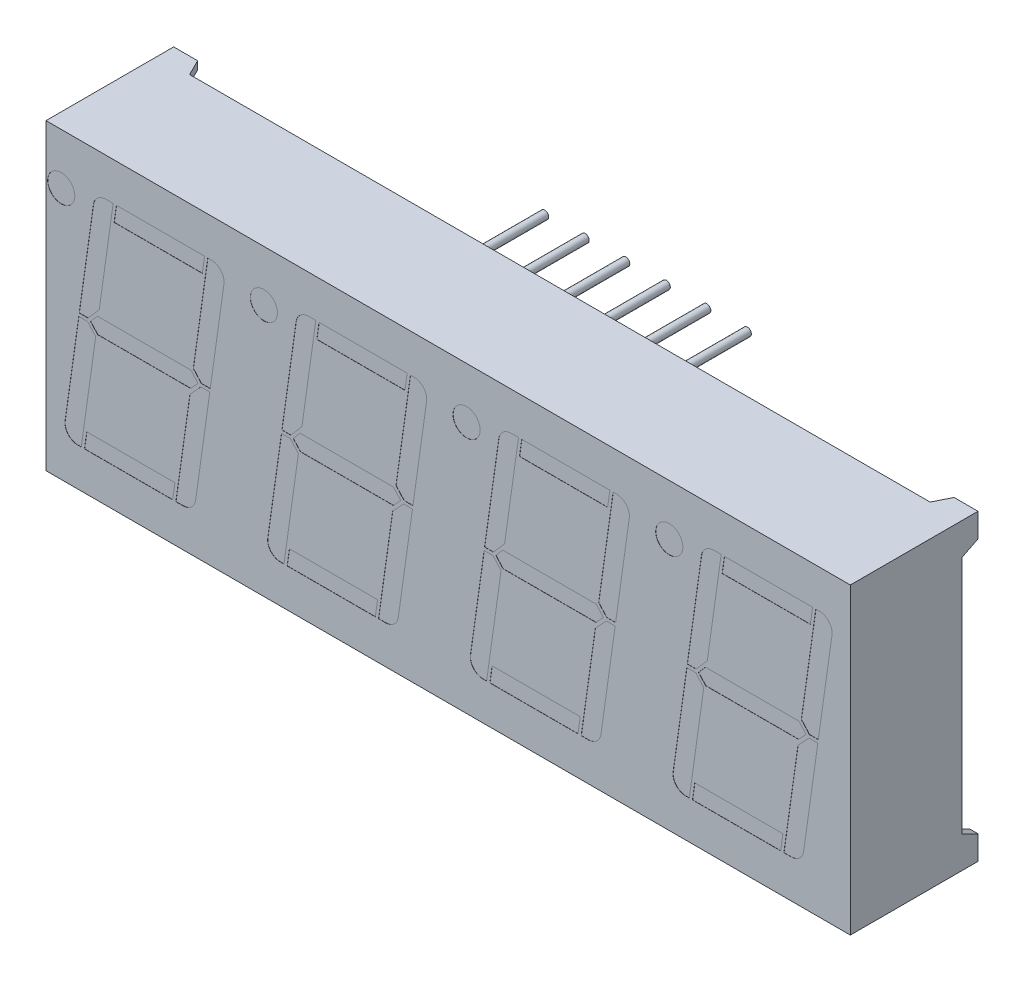
SolidWorks part; units mm, degrees
ref_plane "Front Plane" through (0, 0, 0) normal (0, 0, 1) x (1, 0, 0)
ref_plane "Top Plane" through (0, 0, 0) normal (0, 1, 0) x (1, 0, 0)
ref_plane "Right Plane" through (0, 0, 0) normal (1, 0, 0) x (0, 0, -1)
sketch "Sketch1" plane through (0, 0, 0) normal (0, 1, 0) x (1, 0, 0)
  line L1 (0, 0) -> (50.4, 0)
  line L2 (0, 0) -> (0, 8)
  line L3 (0, 8) -> (50.4, 8)
  line L4 (50.4, 0) -> (50.4, 8)
  dimension "D1" = 8
  dimension "D2" = 50.4
extrude "Boss-Extrude1" add sketch "Sketch1" along normal blind 19
sketch "Sketch2" plane through (0, 0, -8) normal (0, 0, -1) x (-1, 0, 0)
  line L0 (-50.4, 17) -> (-49.9, 17)
  line L1 (-50.4, 19) -> (-50.4, 0) construction
  line L2 (-49.9, 17) -> (-49.9, 18.5)
  line L3 (-49.9, 18.5) -> (-48.4, 18.5)
  line L4 (-48.4, 18.5) -> (-48.4, 19)
  line L5 (-50.4, 19) -> (0, 19) construction
  line L6 (-48.4, 19) -> (-2, 19)
  line L7 (-2, 19) -> (-2, 18.5)
  line L8 (-2, 18.5) -> (-0.5, 18.5)
  line L9 (-0.5, 18.5) -> (-0.5, 17)
  line L10 (-0.5, 17) -> (0, 17)
  line L11 (0, 19) -> (0, 0) construction
  line L12 (0, 17) -> (0, 2)
  line L13 (0, 2) -> (-0.5, 2)
  line L14 (-0.5, 2) -> (-0.5, 0.5)
  line L15 (-0.5, 0.5) -> (-2, 0.5)
  line L16 (-2, 0.5) -> (-2, 0)
  line L17 (-50.4, 0) -> (0, 0) construction
  line L18 (-2, 0) -> (-48.4, 0)
  line L19 (-48.4, 0) -> (-48.4, 0.5)
  line L20 (-48.4, 0.5) -> (-49.9, 0.5)
  line L21 (-49.9, 0.5) -> (-49.9, 2)
  line L22 (-49.9, 2) -> (-50.4, 2)
  line L23 (-50.4, 2) -> (-50.4, 17)
  line L24 (-49.9, 17) -> (-49.9, 2) construction
  line L25 (-48.4, 0.5) -> (-2, 0.5) construction
  line L26 (-0.5, 2) -> (-0.5, 17) construction
  line L27 (-2, 18.5) -> (-48.4, 18.5) construction
  line L28 (-2, 0.5) -> (-2, 18.5) construction
  line L29 (-0.5, 17) -> (-49.9, 17) construction
  line L30 (-48.4, 0.5) -> (-48.4, 18.5) construction
  line L31 (-49.9, 2) -> (-0.5, 2) construction
  dimension "D1" = 0.5
  dimension "D2" = 2
  dimension "D3" = 2
  dimension "D4" = 2
  dimension "D5" = 2
extrude "Cut-Extrude1" cut sketch "Sketch2" against normal blind 1
chamfer "Chamfer1" distance 0.5 distance2 1 8 edges at (50.15, 2, -8) (48.4, 0.25, -8) (2, 0.25, -8) (0.25, 2, -8) (2, 18.75, -8) (0.25, 17, -8) (48.4, 18.75, -8) (50.15, 17, -8) first distance on face at (49.5667, 0.8333, -8) first distance on face at (0.8333, 0.8333, -8) first distance on face at (0.8333, 18.1667, -8) first distance on face at (49.5667, 18.1667, -8)
sketch "Sketch3" plane through (0, 0, -7) normal (0, 0, -1) x (-1, 0, 0)
  line L21 (-49.9, 0.5) -> (-0.5, 0.5)
  line L22 (-49.9, 0.5) -> (-49.9, 18.5)
  line L23 (-49.9, 18.5) -> (-0.5, 18.5)
  line L24 (-0.5, 0.5) -> (-0.5, 18.5)
extrude "Cut-Extrude2" cut sketch "Sketch3" against normal blind 0.1
sketch "Sketch4" plane through (0, 0, -6.9) normal (0, 0, -1) x (-1, 0, 0)
  line L0 (-49.9, 9.5) -> (-0.5, 9.5) construction
  line L1 (-49.9, 2) -> (-49.9, 17) construction
  line L2 (-0.5, 0.5) -> (-0.5, 18.5) construction
  line L3 (-49.9, 17.12) -> (-0.5, 17.12) construction
  line L4 (-49.9, 18.5) -> (-49.9, 0.5) construction
  line L5 (-0.5, 1.88) -> (-49.9, 1.88) construction
  line L6 (-25.2, 1.88) -> (-25.2, 17.12) construction
  line L7 (-26.47, 17.12) -> (-25.2, 15.85) construction
  line L8 (-25.2, 15.85) -> (-23.93, 17.12) construction
  line L9 (-31.55, 17.12) -> (-31.55, 1.88) construction
  line L10 (-29.01, 17.12) -> (-29.01, 1.88) construction
  line L11 (-26.47, 17.12) -> (-26.47, 1.88) construction
  line L12 (-23.93, 17.12) -> (-23.93, 1.88) construction
  line L13 (-21.39, 17.12) -> (-21.39, 1.88) construction
  line L14 (-18.85, 17.12) -> (-18.85, 1.88) construction
  circle A0 centre (-31.55, 17.12) radius 0.25
  circle A1 centre (-29.01, 17.12) radius 0.25
  circle A2 centre (-26.47, 17.12) radius 0.25
  circle A3 centre (-23.93, 17.12) radius 0.25
  circle A4 centre (-21.39, 17.12) radius 0.25
  circle A5 centre (-18.85, 17.12) radius 0.25
  circle A6 centre (-31.55, 1.88) radius 0.25
  circle A7 centre (-29.01, 1.88) radius 0.25
  circle A8 centre (-26.47, 1.88) radius 0.25
  circle A10 centre (-23.93, 1.88) radius 0.25
  circle A11 centre (-21.39, 1.88) radius 0.25
  circle A12 centre (-18.85, 1.88) radius 0.25
  point P30 (-25.2, 9.5)
  dimension "D6" = 0.5
  dimension "D1" = 15.24
  dimension "D2" = 2.54
  dimension "D3" = 2.54
  dimension "D4" = 2.54
  dimension "D5" = 2.54
  dimension "D7" = 2.54
  dimension "D8" = 45
  dimension "D9" = 45
extrude "Boss-Extrude2" add sketch "Sketch4" along normal blind 5.5
sketch "Sketch5" plane through (0, 0, 0) normal (0, 0, 1) x (1, 0, 0)
  line L0 (0, 9.5) -> (50.4, 9.5) construction
  line L1 (0, 19) -> (0, 0) construction
  line L2 (50.4, 19) -> (50.4, 0) construction
  line L3 (49.2488, 15.6987) -> (48.3916, 9.6)
  line L4 (0, 19) -> (50.4, 19) construction
  line L5 (0, 0) -> (50.4, 0) construction
  line L6 (6.15, 19) -> (6.15, 0) construction
  line L7 (18.85, 0) -> (18.85, 19) construction
  line L8 (31.55, 0) -> (31.55, 19) construction
  line L9 (44.25, 0) -> (44.25, 19) construction
  line L10 (25.2, 9.5) -> (25.2, 19) construction
  line L11 (25.2, 14.25) -> (18.85, 14.25) construction
  line L12 (25.2, 14.25) -> (31.55, 14.25) construction
  line L13 (50.4, 16.61) -> (0, 16.61) construction
  line L14 (50.4, 2.39) -> (0, 2.39) construction
  line L15 (49.4, 16.61) -> (49.4, 9.5) construction
  line L16 (49.4, 9.5) -> (49.4, 2.39) construction
  line L17 (48.3916, 9.6) -> (47.8362, 9.6)
  line L18 (47.8362, 9.6) -> (47.3296, 10.1627)
  line L19 (47.3296, 10.1627) -> (48.2357, 16.61)
  line L20 (48.3916, 9.6) -> (48.3635, 9.4) construction
  line L21 (48.3635, 9.4) -> (47.4751, 3.0787)
  line L22 (48.3635, 9.4) -> (47.8081, 9.4)
  line L23 (47.8081, 9.4) -> (47.1185, 8.6605)
  line L24 (47.1185, 8.6605) -> (46.2372, 2.39)
  line L25 (47.6279, 9.5) -> (47.1617, 9)
  line L26 (47.1617, 9) -> (41.3383, 9)
  line L27 (41.3383, 9) -> (40.8881, 9.5)
  line L28 (40.8881, 9.5) -> (41.3223, 10)
  line L29 (41.3223, 10) -> (47.1777, 10)
  line L30 (47.1777, 10) -> (47.6279, 9.5)
  line L31 (44.25, 9) -> (44.25, 10) construction
  line L32 (47.8081, 9.4) -> (47.8362, 9.6) construction
  line L33 (40.709, 9.4) -> (40.7372, 9.6) construction
  line L34 (46.2372, 2.39) -> (46.6829, 2.39)
  line L35 (46.0353, 2.39) -> (46.1758, 3.39)
  line L36 (46.1758, 3.39) -> (40.6521, 3.39)
  line L37 (40.6521, 3.39) -> (40.5115, 2.39)
  line L38 (40.5115, 2.39) -> (46.0353, 2.39)
  line L39 (43.4139, 3.39) -> (43.4139, 2.39) construction
  line L43 (40.1536, 9.4) -> (39.2965, 3.3013)
  line L44 (40.1536, 9.4) -> (40.1818, 9.6) construction
  line L45 (47.3296, 10.1627) -> (47.1185, 8.6605) construction
  line L46 (40.3096, 2.39) -> (41.2157, 8.8373)
  line L47 (40.1818, 9.6) -> (41.0702, 15.9213)
  line L48 (41.436, 10.4048) -> (42.308, 16.61)
  line L49 (41.2157, 8.8373) -> (41.436, 10.4048) construction
  line L50 (41.436, 10.4048) -> (40.7372, 9.6)
  line L51 (40.7372, 9.6) -> (40.1818, 9.6)
  line L52 (44.25, 9.5) -> (44.2005, 9.4505) construction
  line L53 (36.5488, 15.6987) -> (35.6916, 9.6)
  line L54 (41.2157, 8.8373) -> (40.709, 9.4)
  line L55 (40.709, 9.4) -> (40.1536, 9.4)
  line L56 (40.3096, 2.39) -> (40.0887, 2.39)
  line L57 (42.308, 16.61) -> (41.8624, 16.61)
  line L58 (48.2357, 16.61) -> (48.4565, 16.61)
  line L59 (46.1758, 3.39) -> (47.8932, 15.61) construction
  line L60 (40.6521, 3.39) -> (42.3695, 15.61) construction
  line L61 (47.8932, 15.61) -> (42.3695, 15.61)
  line L62 (42.3695, 15.61) -> (42.51, 16.61)
  line L63 (47.8932, 15.61) -> (48.0338, 16.61)
  line L64 (48.0338, 16.61) -> (42.51, 16.61)
  line L65 (35.6916, 9.6) -> (35.1362, 9.6)
  line L66 (35.1362, 9.6) -> (34.6296, 10.1627)
  line L67 (34.6296, 10.1627) -> (35.5357, 16.61)
  line L68 (35.6635, 9.4) -> (34.7751, 3.0787)
  line L69 (35.6635, 9.4) -> (35.1081, 9.4)
  line L70 (35.1081, 9.4) -> (34.4185, 8.6605)
  line L71 (34.4185, 8.6605) -> (33.5372, 2.39)
  line L72 (34.9279, 9.5) -> (34.4617, 9)
  line L73 (34.4617, 9) -> (28.6383, 9)
  line L74 (28.6383, 9) -> (28.1881, 9.5)
  line L75 (28.1881, 9.5) -> (28.6223, 10)
  line L76 (28.6223, 10) -> (34.4777, 10)
  line L77 (34.4777, 10) -> (34.9279, 9.5)
  line L78 (33.5372, 2.39) -> (33.9829, 2.39)
  line L79 (33.3353, 2.39) -> (33.4758, 3.39)
  line L80 (33.4758, 3.39) -> (27.9521, 3.39)
  line L81 (27.9521, 3.39) -> (27.8115, 2.39)
  line L82 (27.8115, 2.39) -> (33.3353, 2.39)
  line L83 (27.4536, 9.4) -> (26.5965, 3.3013)
  line L84 (27.6096, 2.39) -> (28.5157, 8.8373)
  line L85 (27.4818, 9.6) -> (28.3702, 15.9213)
  line L86 (28.736, 10.4048) -> (29.608, 16.61)
  line L87 (28.736, 10.4048) -> (28.0372, 9.6)
  line L88 (28.0372, 9.6) -> (27.4818, 9.6)
  line L89 (28.5157, 8.8373) -> (28.009, 9.4)
  line L90 (28.009, 9.4) -> (27.4536, 9.4)
  line L91 (27.6096, 2.39) -> (27.3887, 2.39)
  line L92 (29.608, 16.61) -> (29.1624, 16.61)
  line L93 (35.5357, 16.61) -> (35.7565, 16.61)
  line L94 (35.1932, 15.61) -> (29.6695, 15.61)
  line L95 (29.6695, 15.61) -> (29.81, 16.61)
  line L96 (35.1932, 15.61) -> (35.3338, 16.61)
  line L97 (35.3338, 16.61) -> (29.81, 16.61)
  line L98 (35.6916, 9.6) -> (35.6635, 9.4) construction
  line L99 (31.55, 9) -> (31.55, 10) construction
  line L100 (35.1081, 9.4) -> (35.1362, 9.6) construction
  line L101 (28.009, 9.4) -> (28.0372, 9.6) construction
  line L102 (30.7139, 3.39) -> (30.7139, 2.39) construction
  line L103 (27.4536, 9.4) -> (27.4818, 9.6) construction
  line L104 (34.6296, 10.1627) -> (34.4185, 8.6605) construction
  line L105 (28.5157, 8.8373) -> (28.736, 10.4048) construction
  line L106 (31.55, 9.5) -> (31.5005, 9.4505) construction
  line L107 (33.4758, 3.39) -> (35.1932, 15.61) construction
  line L108 (27.9521, 3.39) -> (29.6695, 15.61) construction
  line L109 (23.8488, 15.6987) -> (22.9916, 9.6)
  line L110 (22.9916, 9.6) -> (22.4362, 9.6)
  line L111 (22.4362, 9.6) -> (21.9296, 10.1627)
  line L112 (21.9296, 10.1627) -> (22.8357, 16.61)
  line L113 (22.9635, 9.4) -> (22.0751, 3.0787)
  line L114 (22.9635, 9.4) -> (22.4081, 9.4)
  line L115 (22.4081, 9.4) -> (21.7185, 8.6605)
  line L116 (21.7185, 8.6605) -> (20.8372, 2.39)
  line L117 (22.2279, 9.5) -> (21.7617, 9)
  line L118 (21.7617, 9) -> (15.9383, 9)
  line L119 (15.9383, 9) -> (15.4881, 9.5)
  line L120 (15.4881, 9.5) -> (15.9223, 10)
  line L121 (15.9223, 10) -> (21.7777, 10)
  line L122 (21.7777, 10) -> (22.2279, 9.5)
  line L123 (20.8372, 2.39) -> (21.2829, 2.39)
  line L124 (20.6353, 2.39) -> (20.7758, 3.39)
  line L125 (20.7758, 3.39) -> (15.2521, 3.39)
  line L126 (15.2521, 3.39) -> (15.1115, 2.39)
  line L127 (15.1115, 2.39) -> (20.6353, 2.39)
  line L128 (14.7536, 9.4) -> (13.8965, 3.3013)
  line L129 (14.9096, 2.39) -> (15.8157, 8.8373)
  line L130 (14.7818, 9.6) -> (15.6702, 15.9213)
  line L131 (16.036, 10.4048) -> (16.908, 16.61)
  line L132 (16.036, 10.4048) -> (15.3372, 9.6)
  line L133 (15.3372, 9.6) -> (14.7818, 9.6)
  line L134 (15.8157, 8.8373) -> (15.309, 9.4)
  line L135 (15.309, 9.4) -> (14.7536, 9.4)
  line L136 (14.9096, 2.39) -> (14.6887, 2.39)
  line L137 (16.908, 16.61) -> (16.4624, 16.61)
  line L138 (22.8357, 16.61) -> (23.0565, 16.61)
  line L139 (22.4932, 15.61) -> (16.9695, 15.61)
  line L140 (16.9695, 15.61) -> (17.11, 16.61)
  line L141 (22.4932, 15.61) -> (22.6338, 16.61)
  line L142 (22.6338, 16.61) -> (17.11, 16.61)
  line L143 (22.9916, 9.6) -> (22.9635, 9.4) construction
  line L144 (18.85, 9) -> (18.85, 10) construction
  line L145 (22.4081, 9.4) -> (22.4362, 9.6) construction
  line L146 (15.309, 9.4) -> (15.3372, 9.6) construction
  line L147 (18.0139, 3.39) -> (18.0139, 2.39) construction
  line L148 (14.7536, 9.4) -> (14.7818, 9.6) construction
  line L149 (21.9296, 10.1627) -> (21.7185, 8.6605) construction
  line L150 (15.8157, 8.8373) -> (16.036, 10.4048) construction
  line L151 (18.85, 9.5) -> (18.8005, 9.4505) construction
  line L152 (20.7758, 3.39) -> (22.4932, 15.61) construction
  line L153 (15.2521, 3.39) -> (16.9695, 15.61) construction
  line L154 (11.1488, 15.6987) -> (10.2916, 9.6)
  line L155 (10.2916, 9.6) -> (9.7362, 9.6)
  line L156 (9.7362, 9.6) -> (9.2296, 10.1627)
  line L157 (9.2296, 10.1627) -> (10.1357, 16.61)
  line L158 (10.2635, 9.4) -> (9.3751, 3.0787)
  line L159 (10.2635, 9.4) -> (9.7081, 9.4)
  line L160 (9.7081, 9.4) -> (9.0185, 8.6605)
  line L161 (9.0185, 8.6605) -> (8.1372, 2.39)
  line L162 (9.5279, 9.5) -> (9.0617, 9)
  line L163 (9.0617, 9) -> (3.2383, 9)
  line L164 (3.2383, 9) -> (2.7881, 9.5)
  line L165 (2.7881, 9.5) -> (3.2223, 10)
  line L166 (3.2223, 10) -> (9.0777, 10)
  line L167 (9.0777, 10) -> (9.5279, 9.5)
  line L168 (8.1372, 2.39) -> (8.5829, 2.39)
  line L169 (7.9353, 2.39) -> (8.0758, 3.39)
  line L170 (8.0758, 3.39) -> (2.5521, 3.39)
  line L171 (2.5521, 3.39) -> (2.4115, 2.39)
  line L172 (2.4115, 2.39) -> (7.9353, 2.39)
  line L173 (2.0536, 9.4) -> (1.1965, 3.3013)
  line L174 (2.2096, 2.39) -> (3.1157, 8.8373)
  line L175 (2.0818, 9.6) -> (2.9702, 15.9213)
  line L176 (3.336, 10.4048) -> (4.208, 16.61)
  line L177 (3.336, 10.4048) -> (2.6372, 9.6)
  line L178 (2.6372, 9.6) -> (2.0818, 9.6)
  line L179 (3.1157, 8.8373) -> (2.609, 9.4)
  line L180 (2.609, 9.4) -> (2.0536, 9.4)
  line L181 (2.2096, 2.39) -> (1.9887, 2.39)
  line L182 (4.208, 16.61) -> (3.7624, 16.61)
  line L183 (10.1357, 16.61) -> (10.3565, 16.61)
  line L184 (9.7932, 15.61) -> (4.2695, 15.61)
  line L185 (4.2695, 15.61) -> (4.41, 16.61)
  line L186 (9.7932, 15.61) -> (9.9338, 16.61)
  line L187 (9.9338, 16.61) -> (4.41, 16.61)
  line L188 (10.2916, 9.6) -> (10.2635, 9.4) construction
  line L189 (6.15, 9) -> (6.15, 10) construction
  line L190 (9.7081, 9.4) -> (9.7362, 9.6) construction
  line L191 (2.609, 9.4) -> (2.6372, 9.6) construction
  line L192 (5.3139, 3.39) -> (5.3139, 2.39) construction
  line L193 (2.0536, 9.4) -> (2.0818, 9.6) construction
  line L194 (9.2296, 10.1627) -> (9.0185, 8.6605) construction
  line L195 (3.1157, 8.8373) -> (3.336, 10.4048) construction
  line L196 (6.15, 9.5) -> (6.1005, 9.4505) construction
  line L197 (8.0758, 3.39) -> (9.7932, 15.61) construction
  line L198 (2.5521, 3.39) -> (4.2695, 15.61) construction
  line L199 (39.0545, 16.61) -> (39.0545, 15.81) construction
  line L200 (39.0545, 15.81) -> (41.0545, 15.81) construction
  line L201 (26.3545, 15.81) -> (28.3545, 15.81) construction
  line L202 (26.3545, 15.81) -> (26.3545, 16.61) construction
  arc A0 (48.4565, 16.61) -> (49.2488, 15.6987) centre (48.4565, 15.81) cw
  arc A2 (47.4751, 3.0787) -> (46.6829, 2.39) centre (46.6829, 3.19) cw
  arc A3 (39.2965, 3.3013) -> (40.0887, 2.39) centre (40.0887, 3.19) ccw
  arc A4 (41.8624, 16.61) -> (41.0702, 15.9213) centre (41.8624, 15.81) ccw
  arc A5 (35.7565, 16.61) -> (36.5488, 15.6987) centre (35.7565, 15.81) cw
  arc A6 (34.7751, 3.0787) -> (33.9829, 2.39) centre (33.9829, 3.19) cw
  arc A7 (26.5965, 3.3013) -> (27.3887, 2.39) centre (27.3887, 3.19) ccw
  arc A8 (29.1624, 16.61) -> (28.3702, 15.9213) centre (29.1624, 15.81) ccw
  arc A9 (23.0565, 16.61) -> (23.8488, 15.6987) centre (23.0565, 15.81) cw
  arc A10 (22.0751, 3.0787) -> (21.2829, 2.39) centre (21.2829, 3.19) cw
  arc A11 (13.8965, 3.3013) -> (14.6887, 2.39) centre (14.6887, 3.19) ccw
  arc A12 (16.4624, 16.61) -> (15.6702, 15.9213) centre (16.4624, 15.81) ccw
  arc A13 (10.3565, 16.61) -> (11.1488, 15.6987) centre (10.3565, 15.81) cw
  arc A14 (9.3751, 3.0787) -> (8.5829, 2.39) centre (8.5829, 3.19) cw
  arc A15 (1.1965, 3.3013) -> (1.9887, 2.39) centre (1.9887, 3.19) ccw
  arc A16 (3.7624, 16.61) -> (2.9702, 15.9213) centre (3.7624, 15.81) ccw
  circle A17 centre (39.0545, 15.81) radius 0.85
  circle A18 centre (26.3545, 15.81) radius 0.85
  circle A19 centre (13.6545, 15.81) radius 0.85
  circle A20 centre (0.9545, 15.81) radius 0.85
  point P36 (48.3776, 9.5)
  point P51 (44.25, 9.5)
  point P66 (43.4139, 3.39)
  point P67 (40.1677, 9.5)
  point P231 (0, 0)
  point P239 (28.009, 15.81)
  dimension "D8" = 1.13
  dimension "D10" = 0.8
  dimension "D20" = 0.8
  dimension "D24" = 1.13
  dimension "D23" = 1.13
  dimension "D13" = 0.8
  dimension "D22" = 0.8
  dimension "D32" = 1.7
  dimension "D1" = 12.7
  dimension "D2" = 12.7
  dimension "D3" = 12.7
  dimension "D4" = 14.22
  dimension "D5" = 1
  dimension "D6" = 8
  dimension "D7" = 0.55
  dimension "D9" = 0.55
  dimension "D11" = 0.1
  dimension "D12" = 1
  dimension "D14" = 1
  dimension "D15" = 0.2
  dimension "D16" = 0.1
  dimension "D17" = 0.2
  dimension "D18" = 8.13
  dimension "D19" = 130
  dimension "D21" = 145
  dimension "D25" = 1.13
  dimension "D26" = 130
  dimension "D27" = 0.2
  dimension "D28" = 0.2
  dimension "D30" = 0.8
  dimension "D31" = 2
  dimension "D34" = 2
  dimension "D29" = 4
  dimension "D33" = 4
extrude "Cut-Extrude3" cut sketch "Sketch5" against normal blind 0.01
